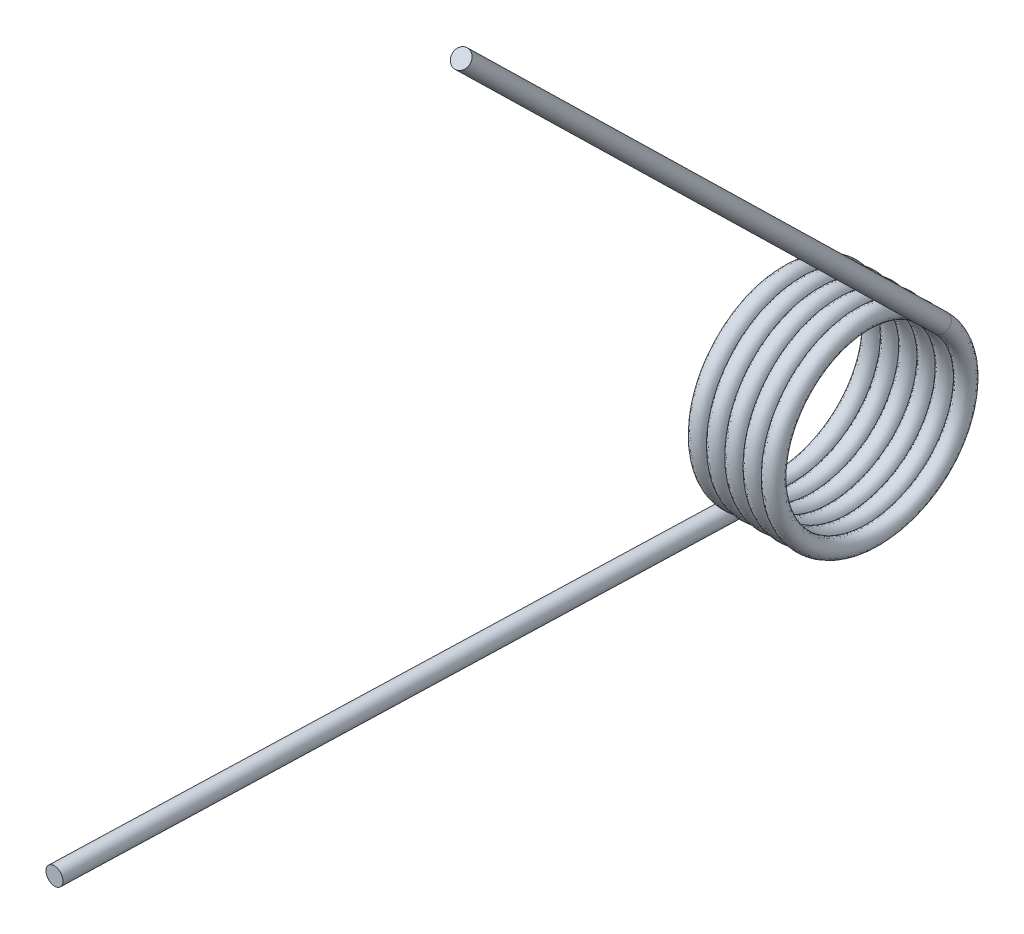
SolidWorks part; units mm, degrees
ref_plane "xy_plane" through (0, 0, 0) normal (0, 0, 1) x (1, 0, 0)
ref_plane "zx_plane" through (0, 0, 0) normal (0, 1, 0) x (1, 0, 0)
ref_plane "yz_plane" through (0, 0, 0) normal (1, 0, 0) x (0, 0, -1)
ref_axis "x_axis" through (-1.3397, 0, 0) along (1, 0, 0)
ref_axis "y_axis" through (0, -4.2648, 0) along (0, 1, 0)
ref_axis "z_axis" through (0, 0, -27.9381) along (0, 0, 1)
sketch "Sketch1" plane through (0, 0, 0) normal (1, 0, 0) x (0, 0, -1)
  line L0 (0, 0) -> (0, -2.9891) construction
  line L1 (0, -2.9891) -> (0, -3.3066) construction
  line L2 (0, -3.3066) -> (0, -3.6241) construction
  circle A0 centre (0, 0) radius 2.9891 construction
  circle A1 centre (0, 0) radius 3.6241 construction
  circle A2 centre (0, 0) radius 3.3066
  circle A3 centre (0, -3.3066) radius 0.3175 construction
  circle A4 centre (0, 0) radius 2.5781 construction
sketch "turningAngleFollower_sketch" plane through (0, 0, 0) normal (1, 0, 0) x (0, 0, -1)
  line L0 (2.3121, 2.3638) -> (-15.8458, 20.1247)
  line L1 (27.9381, 0) -> (-27.9381, 0) construction
  circle A0 centre (0, 0) radius 3.3066 construction
  dimension "D1" = 25.4
  dimension "turningAngle" = 135.633
curve "Helix/Spiral1" pitch 0.6604 height 3.5508 radius 3.3066 centre (0, 0, 0) axis (1, 0, 0) start towards (0, 0, -1) parameters "height"=3.5508, "pitch"=0.6604
ref_plane "Plane1" through (0, -3.3066, 0) normal (0.0318, 0, -0.9995) x (-0.9995, 0, -0.0318)
sketch "Sketch2" plane through (0, -3.3066, 0) normal (0.0318, 0, -0.9995) x (-0.9995, 0, -0.0318)
  circle A0 centre (0, 0) radius 0.3175
  dimension "D1" = 0.635
sweep "Sweep1" add profiles "Sketch2" path "Helix/Spiral1"
sketch "Sketch3" plane through (0, 0, 0) normal (-0.0318, 0, 0.9995) x (0.9995, 0, 0.0318)
  circle A1 centre (0, -3.3066) radius 0.3175
  circle A2 centre (0, -3.3066) radius 0.3175
  dimension "D1" = 0
extrude "Extrude1" add sketch "Sketch3" along normal blind 25.4
sketch "Sketch4" plane through (0.0036, 0.0788, 0.0806) normal (0.0318, 0.6989, 0.7145) x (0.5048, 0.6058, -0.615)
  circle A1 centre (4.6464, -1.393) radius 0.3175
  circle A2 centre (4.6464, -1.393) radius 0.3175
  dimension "D1" = 0
extrude "Extrude2" add sketch "Sketch4" along normal blind 25.4
sketch "Sketch5" plane through (0, 0, 0) normal (1, 0, 0) x (0, 0, -1)
  circle A0 centre (0, 0) radius 2.5781 construction
  circle A1 centre (0, 0) radius 2.5781
ref_point "helixStartPoint" parameters "D1"=0
sketch "arm1PlaneNormal_sketch" plane through (0, 0, 0) normal (1, 0, 0) x (0, 0, -1)
  line L0 (0, 0) -> (0, -3.3066)
  point P2 (0, 0)
  point P4 (-1.9214, -8.0287)
  point P5 (0, 0)
  point P7 (0, 0)
ref_axis "arm1PlaneNormal_axis" through (0, 0, 0) along (0, -1, 0)
ref_plane "arm1_plane" through (0, -3.3066, 0) normal (0, -1, 0) x (-1, 0, 0)
ref_point "helixEndPoint"
sketch "arm2PlaneNormal_sketch" plane through (0, 0, 0) normal (1, 0, 0) x (0, -1, 0)
  line L0 (0, 0) -> (-2.3638, 2.3121)
  point P2 (0, 0)
  point P3 (2.1279, 0.1343)
  point P5 (0, 0)
ref_axis "arm2PlaneNormal_axis" through (0, 0, 0) along (0, 0.7149, -0.6992)
ref_plane "arm2_plane" through (3.5508, 2.3638, -2.3121) normal (0, 0.7149, -0.6992) x (-1, 0, 0)
equation "\"pitch@Helix/Spiral1\"= \"helixPitch\""
equation "\"D1@Sketch2\" = \"wireDiameter\""
equation "\"D1@Extrude2\"=\"Leg Length@Extrude1\""
equation "\"wireDiameter\"= 0.025in"
equation "\"relaxedNumberOfTurns\"= 5"
equation "\"relaxedHelixDiameter\"= \"relaxedSpringOD\" - \"wireDiameter\""
equation "\"relaxedSpringOD\"= 0.305in"
equation "\"helixLength\"= \"relaxedNumberOfTurns\" * sqr ( ( PI * \"relaxedHelixDiameter\" ) ^ 2 + \"helixPitch\" ^ 2 )"
equation "\"helixPitch\"= \"wireDiameter\" + 0.001in"
equation "\"numberOfTurns\"= \"relaxedNumberOfTurns\" + \"turningAngle\" / 360deg"
equation "\"helixDiameter\"= 1 / PI * sqr ( ( \"helixLength\" / \"numberOfTurns\" ) ^ 2 - \"helixPitch\" ^ 2 )"
equation "\"springOD\"= \"helixDiameter\" + \"wireDiameter\""
equation "\"Spring OD@Sketch1\"= \"springOD\""
equation "\"Wire Dia@Sketch1\"= \"wireDiameter\""
equation "\"Number Coils@Helix/Spiral1\"= \"numberOfTurns\""
equation "\"turningAngle\"= \"turningAngle@turningAngleFollower_sketch\""
